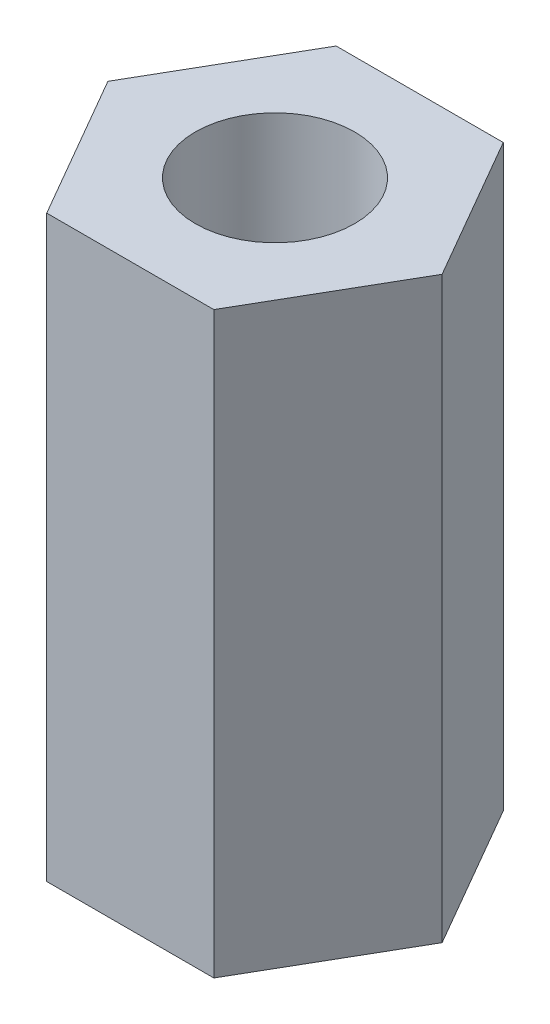
SolidWorks part; units mm, degrees
ref_plane "Front Plane" through (0, 0, 0) normal (0, 0, 1) x (1, 0, 0)
ref_plane "Top Plane" through (0, 0, 0) normal (0, 1, 0) x (1, 0, 0)
ref_plane "Right Plane" through (0, 0, 0) normal (1, 0, 0) x (0, 0, -1)
other "Default"
sketch "Sketch1" plane through (0, 0, 0) normal (0, 1, 0) x (1, 0, 0)
  line L1 (2.8868, 0) -> (1.4434, 2.5)
  line L2 (1.4434, 2.5) -> (-1.4434, 2.5)
  line L3 (-1.4434, 2.5) -> (-2.8868, 0)
  line L4 (-2.8868, 0) -> (-1.4434, -2.5)
  line L5 (-1.4434, -2.5) -> (1.4434, -2.5)
  line L6 (1.4434, -2.5) -> (2.8868, 0)
  circle A0 centre (0, 0) radius 2.5 construction
  circle A1 centre (0, 0) radius 1.375
  dimension "D1" = 2.75
  dimension "D2" = 5
extrude "Boss-Extrude1" add sketch "Sketch1" along normal mid plane 10
